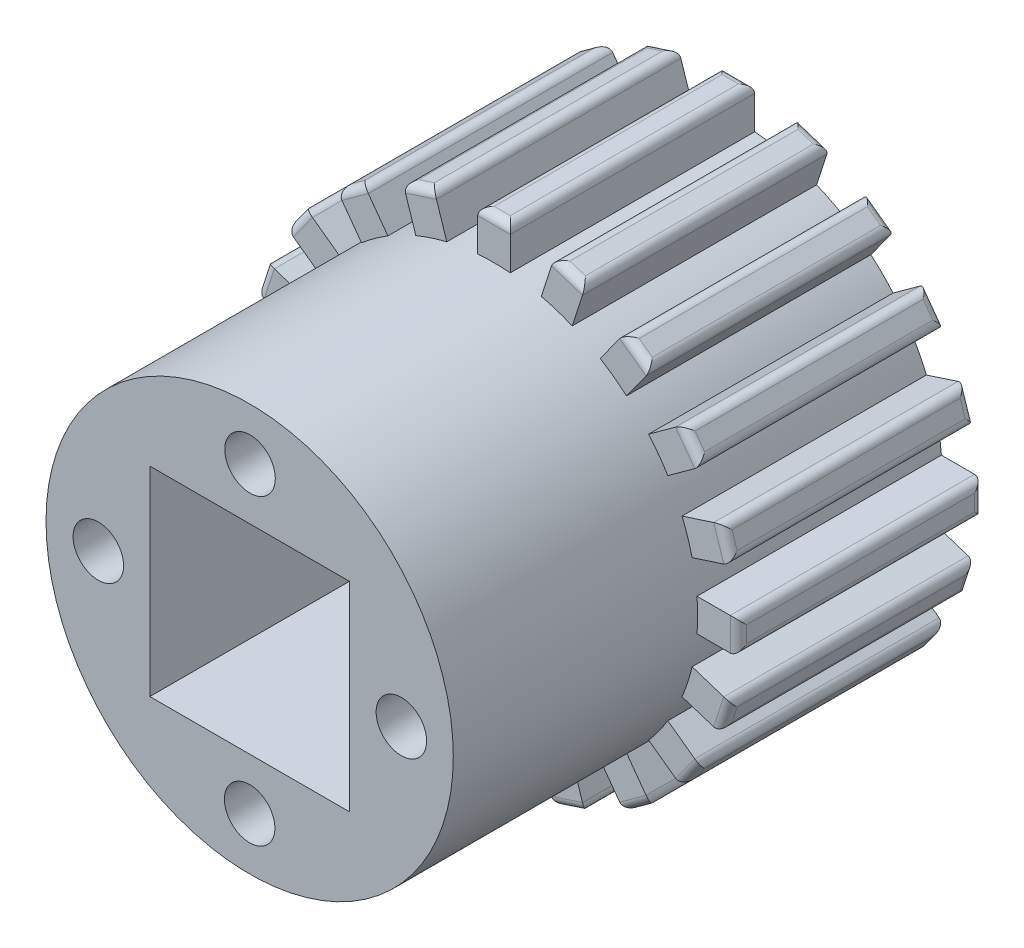
SolidWorks part; units mm, degrees
ref_plane "Front Plane" through (0, 0, 0) normal (0, 0, 1) x (1, 0, 0)
ref_plane "Top Plane" through (0, 0, 0) normal (0, 1, 0) x (1, 0, 0)
ref_plane "Right Plane" through (0, 0, 0) normal (1, 0, 0) x (0, 0, -1)
sketch "Sketch1" plane through (0, 0, 0) normal (0, 0, 1) x (1, 0, 0)
  circle A0 centre (0, 0) radius 12.5
  dimension "D2" = 25
extrude "Boss-Extrude1" add sketch "Sketch1" along normal mid plane 15
sketch "Sketch4" plane through (0, 0, 7.5) normal (0, 0, 1) x (1, 0, 0)
  line L0 (16.5, 0) -> (-16.5, 0) construction
  line L2 (-1, 0) -> (1, 0)
  line L3 (0, 0) -> (0, 15.8331) construction
  line L4 (-1, 0) -> (-1, 15)
  line L5 (-1, 15) -> (1, 15)
  line L6 (1, 0) -> (1, 15)
  circle A3 centre (0, 0) radius 12.5 construction
  point P9 (0, 0)
  dimension "D2" = 2
  dimension "D1" = 15
extrude "Boss-Extrude3" add sketch "Sketch4" against normal up to surface (15 mm away) up to face at (12.5, 0, -7.5)
fillet "Fillet1" radius 0.5 4 edges at (0, 15, 7.5) (0, 15, -7.5) (-1, 15, 0) (1, 15, 0)
pattern_circular "CirPattern7" count 20 over 360 about axis through (0, 0, -7.5) along (0, 0, 1) of "Boss-Extrude3", "Fillet1"
sketch "Sketch10" plane through (0, 0, 7.5) normal (0, 0, 1) x (1, 0, 0)
  circle A0 centre (0, 0) radius 12.5
  dimension "D1" = 25
extrude "Boss-Extrude4" add sketch "Sketch10" along normal blind 15
sketch "Sketch8" plane through (0, 0, 7.5) normal (0, 0, 1) x (1, 0, 0)
  line L2 (-6.125, 6.125) -> (6.125, 6.125)
  line L3 (-6.125, 6.125) -> (-6.125, -6.125)
  line L4 (-6.125, -6.125) -> (6.125, -6.125)
  line L5 (6.125, 6.125) -> (6.125, -6.125)
  line L6 (-6.125, 6.125) -> (6.125, -6.125) construction
  line L7 (-6.125, -6.125) -> (6.125, 6.125) construction
  point P5 (0, 0)
  point P14 (0, 0)
  dimension "D1" = 12.25
extrude "Cut-Extrude3" cut sketch "Sketch8" against normal up to next from surface starting at face at (12.5, 0, 22.5)
sketch "Sketch9" plane through (0, 0, 7.5) normal (0, 0, 1) x (1, 0, 0)
  line L0 (16.5, 0) -> (-16.5, 0) construction
  line L1 (6.125, -6.125) -> (6.125, 6.125) construction
  circle A0 centre (9.3125, 0) radius 1.55
  circle A1 centre (0, -9.2875) radius 1.55
  circle A2 centre (-9.2875, 0.025) radius 1.55
  circle A3 centre (0.025, 9.3125) radius 1.55
  point P14 (0.0125, 0.0125)
  dimension "D1" = 3.1
  dimension "D2" = 3.1875
  dimension "D3" = 4
extrude "Cut-Extrude4" cut sketch "Sketch9" against normal through all from surface starting at face at (12.5, 0, 22.5)
equation "\"drumDiameter\"= 25"
equation "\"D2@Sketch1\"=\"drumDiameter\""
equation "\"drumLength\"= 15"
equation "\"foamThickness\"= 5"
equation "\"drumAbove\"= 0.6"
equation "\"holderThicc\" = 2"
equation "\"D2@Sketch4\"=\"holderThicc\""
equation "\"D1@Boss-Extrude1\"=\"drumLength\""
equation "\"squareBarLength\"= 12.25"
equation "\"D1@Sketch8\"=\"squareBarLength\""
equation "\"D2@Sketch9\"=(\"drumDiameter\"/2-\"squareBarLength\"/2)/2"
equation "\"D1@Sketch10\"=\"drumDiameter\""
equation "\"D1@Boss-Extrude4\"=\"drumLength\""
equation "\"toothlen\"= 2.5"
equation "\"D1@Sketch4\"=\"drumDiameter\"/2 + \"toothlen\""
